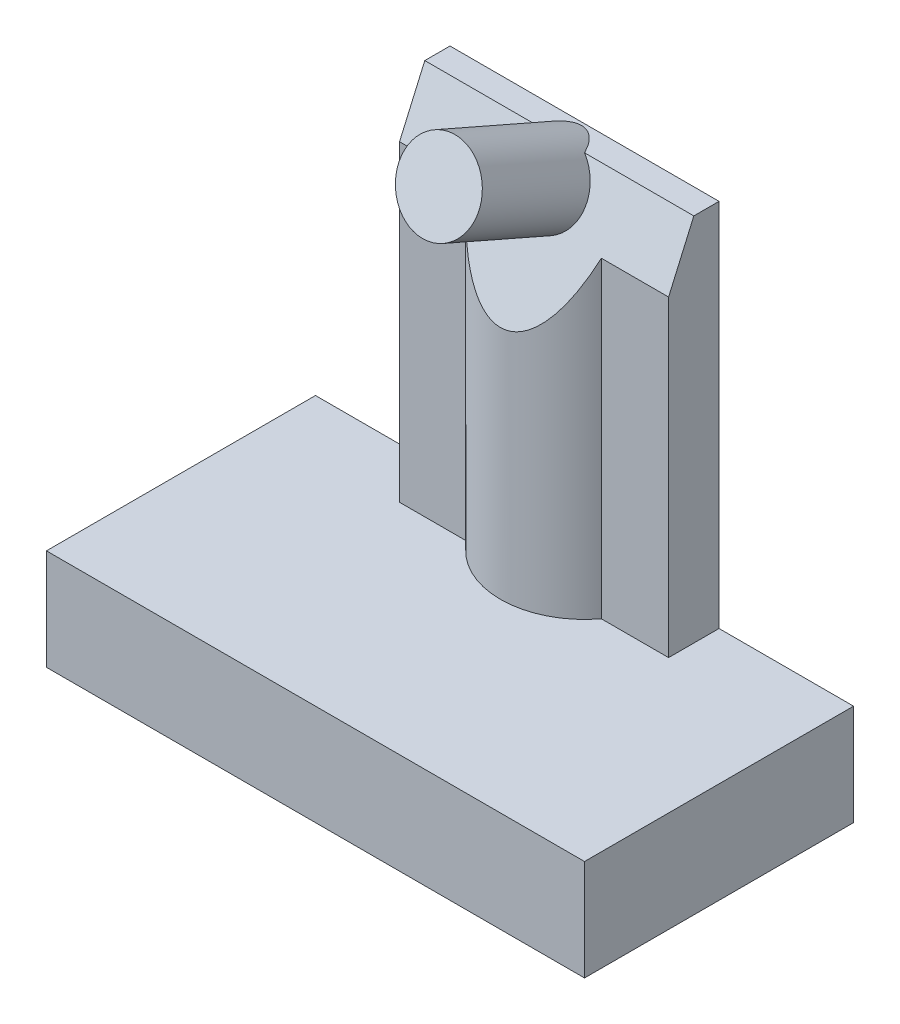
SolidWorks part; units mm, degrees
ref_plane "Front Plane" through (0, 0, 0) normal (0, 0, 1) x (1, 0, 0)
ref_plane "Top Plane" through (0, 0, 0) normal (0, 1, 0) x (1, 0, 0)
ref_plane "Right Plane" through (0, 0, 0) normal (1, 0, 0) x (0, 0, -1)
sketch "Sketch1" plane through (0, 0, 0) normal (0, 1, 0) x (1, 0, 0)
  line L1 (-8, 4) -> (8, 4)
  line L2 (-8, 4) -> (-8, -4)
  line L3 (-8, -4) -> (8, -4)
  line L4 (8, 4) -> (8, -4)
  line L5 (-8, 4) -> (8, -4) construction
  line L6 (-8, -4) -> (8, 4) construction
  dimension "D1" = 16
  dimension "D2" = 8
extrude "Boss-Extrude1" add sketch "Sketch1" along normal blind 3
shell "Shell1" thickness 1 removed face at (0, 0, 0)
sketch "Sketch2" plane through (0, 2, 0) normal (0, -1, 0) x (1, 0, 0)
  circle A0 centre (0, 0) radius 0.8
  circle A1 centre (0, 0) radius 1.5
  dimension "D1" = 3
  dimension "D2" = 1.6
extrude "Boss-Extrude2" add sketch "Sketch2" along normal blind 2
sketch "Sketch3" plane through (0, 3, 0) normal (0, 1, 0) x (1, 0, 0)
  line L0 (0, 0) -> (0, 4) construction
  line L1 (8, 4) -> (-8, 4) construction
  line L2 (-4, 4) -> (4, 4)
  line L3 (4, 4) -> (4, 2.5)
  line L4 (4, 2.5) -> (2, 2.5)
  line L5 (0, 2.5) -> (-0.0455, 2.5)
  line L6 (-4, 2.5) -> (-2, 2.5)
  line L7 (-4, 4) -> (-4, 2.5)
  arc A0 (-2, 2.5) -> (2, 2.5) centre (0, 4) ccw
  line M7 (8, 4) -> (-8, 4)
  dimension "D1" = 5
  dimension "D2" = 1.5
  dimension "D3" = 4
extrude "Boss-Extrude3" add sketch "Sketch3" along normal blind 11 contours L0 A0 L4 L3 M7 | A0 L0 L2 L7 L6 region at (-1.7685, 3, -3.0312) region at (1.7685, 3, -3.0312)
sketch "Sketch4" plane through (4, 0, 0) normal (1, 0, 0) x (0, 0, -1)
  line L0 (3.25, 14) -> (1.5, 14)
  line L1 (4, 14) -> (2.5, 14) construction
  line L2 (1.5, 14) -> (1.5, 10)
  line L3 (1.5, 14) -> (1.5, 3) construction
  line L4 (1.5, 10) -> (3.25, 14)
  dimension "D1" = 4
extrude "Cut-Extrude1" cut sketch "Sketch4" against normal through all
sketch "Sketch5" plane through (0, 1.0557, 2.4131) normal (0, 0.4008, 0.9162) x (1, 0, 0)
  line L0 (-4, 13.1933) -> (4, 13.1933) construction
  line L1 (-4, 12.2577) -> (-4, 14.1289) construction
  line L2 (4, 12.2577) -> (4, 14.1289) construction
  line L3 (0, 14.1289) -> (0, 9.7628) construction
  line L4 (4, 14.1289) -> (-4, 14.1289) construction
  circle A0 centre (0, 13.1933) radius 1.2
  ellipse E0 centre (0, 16) end of major axis (0, 9.7628) minor radius 2.5 (-2, 12.2577) -> (2, 12.2577) ccw construction
  dimension "D1" = 2.4
extrude "Boss-Extrude4" add sketch "Sketch5" against normal up to next and the other way blind 3.5 contours A0
